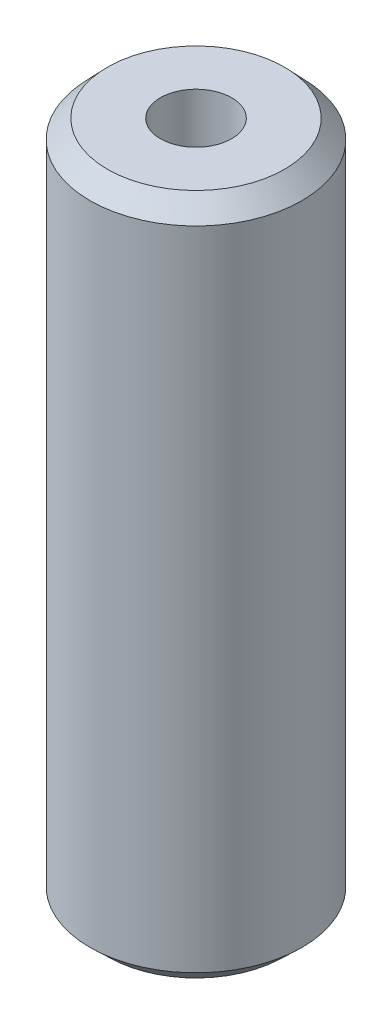
SolidWorks part; units mm, degrees
ref_plane "Front Plane" through (0, 0, 0) normal (0, 0, 1) x (1, 0, 0)
ref_plane "Top Plane" through (0, 0, 0) normal (0, 1, 0) x (1, 0, 0)
ref_plane "Right Plane" through (0, 0, 0) normal (1, 0, 0) x (0, 0, -1)
sketch "Sketch1" plane through (0, 0, 0) normal (0, 1, 0) x (1, 0, 0)
  circle A0 centre (0, 0) radius 12.5
  dimension "SHAFT_OD" = 25
extrude "Boss-Extrude1" add sketch "Sketch1" along normal blind 80.4844
sketch "Sketch2" plane through (0, 0, 0) normal (0, 1, 0) x (1, 0, 0)
  circle A0 centre (0, 0) radius 4.1965
  dimension "BORE_D" = 8.3929
extrude "Cut-Extrude1" cut sketch "Sketch2" along normal through all
chamfer "Chamfer1" distance 2.1673 angle 43.574 2 edges at (0, 80.4844, 12.5) (0, 0, 12.5) first distance on face at (0, 80.4844, 12.5) first distance on face at (0, 0, 4.1965)
